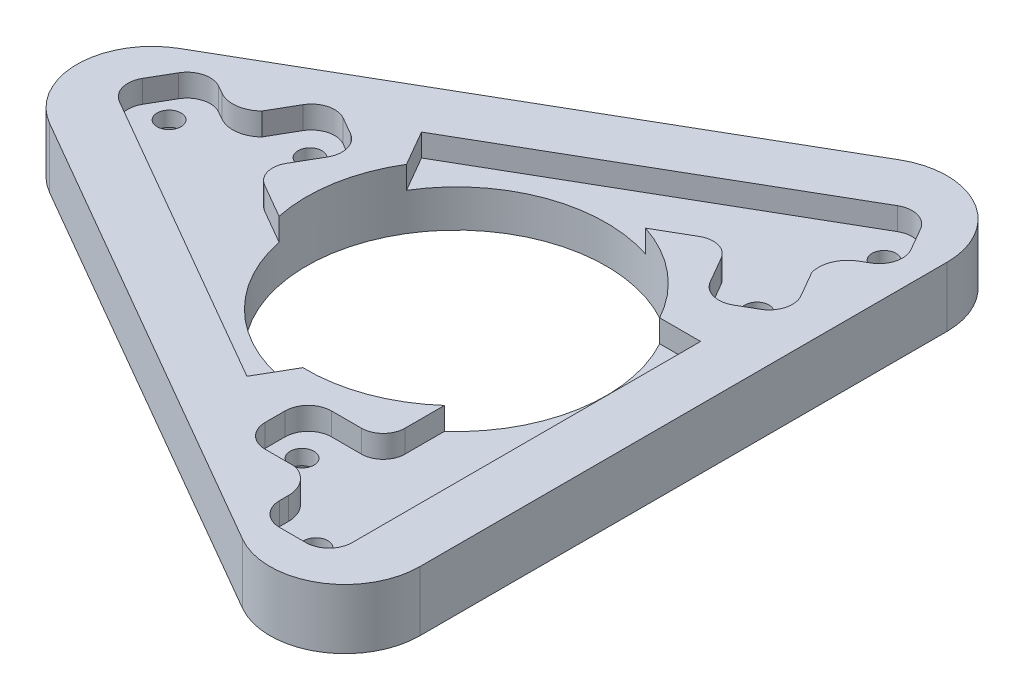
SolidWorks part; units mm, degrees
ref_plane "Plan de face" through (0, 0, 0) normal (0, 0, 1) x (1, 0, 0)
ref_plane "Plan de dessus" through (0, 0, 0) normal (0, 1, 0) x (1, 0, 0)
ref_plane "Plan de droite" through (0, 0, 0) normal (1, 0, 0) x (0, 0, -1)
sketch "Esquisse1" plane through (0, 0, 0) normal (0, 1, 0) x (1, 0, 0)
  line L7 (14.4338, 0) -> (-7.2169, 12.5) construction
  line L8 (-7.2169, 12.5) -> (-7.2169, -12.5) construction
  line L9 (-7.2169, -12.5) -> (14.4338, 0) construction
  circle A0 centre (0, 0) radius 7.2169 construction
  circle A1 centre (-7.2169, -12.5) radius 2 construction
  circle A2 centre (-7.2169, 12.5) radius 2 construction
  circle A3 centre (14.4338, 0) radius 2 construction
  dimension "D2" = 4
  dimension "D3" = 4
  dimension "D4" = 4
  dimension "D1" = 25
sketch "Esquisse4" plane through (0, 0, 0) normal (0, 1, 0) x (1, 0, 0)
  line L0 (14.8238, 7.28) -> (16.4238, 7.28) construction
  line L1 (16.4238, 7.28) -> (16.4238, -22.72) construction
  line L2 (16.4238, -22.72) -> (14.8238, -22.72) construction
  line L3 (14.8238, -22.72) -> (14.8238, 7.28) construction
  line L7 (-1.1072, -16.4777) -> (-27.088, -1.4777) construction
  line L8 (-27.088, -1.4777) -> (-27.888, -2.8634) construction
  line L9 (-7.2169, 12.5) -> (-7.2169, -12.5) construction
  line L10 (-13.7165, 9.1977) -> (-14.5165, 10.5834) construction
  line L11 (-14.5165, 10.5834) -> (11.4642, 25.5834) construction
  line L12 (11.4642, 25.5834) -> (12.2642, 24.1977) construction
  line L13 (12.2642, 24.1977) -> (-13.7165, 9.1977) construction
  line L14 (-7.2169, -12.5) -> (14.4338, 0) construction
  line L15 (-27.888, -2.8634) -> (-1.9072, -17.8634) construction
  line L16 (-1.9072, -17.8634) -> (-1.1072, -16.4777) construction
  dimension "D2" = 1.6
  dimension "D3" = 30
  dimension "D4" = 7.28
  dimension "D5" = 0.39
  dimension "D6" = 60
  dimension "D7" = 0.39
  dimension "D8" = 1.6
  dimension "D9" = 1.6
  dimension "D10" = 0.39
  dimension "D11" = 7.28
  dimension "D12" = 30
  dimension "D13" = 1.6
  dimension "D14" = 7.28
  dimension "D15" = 30
  dimension "D16" = 1.6
  dimension "D17" = 60
sketch "Esquisse5" plane through (0, 0, 0) normal (0, 1, 0) x (1, 0, 0)
  line L0 (-7.2169, 12.5) -> (-7.2169, -12.5) construction
  line L1 (30.3109, -52.5) -> (30.3109, 52.5)
  line L2 (30.3109, 52.5) -> (-60.6218, 0)
  line L3 (-60.6218, 0) -> (30.3109, -52.5)
  circle A1 centre (0, 0) radius 20
  circle A2 centre (0, 0) radius 30.3109 construction
  dimension "D1" = 105
  dimension "D2" = 40
extrude "Boss.-Extru.1" add sketch "Esquisse5" along normal blind 8
ref_axis "Axe1" through (0, 130.0156, 0) along (0, -1, 0)
sketch "Esquisse8" plane through (0, 8, 0) normal (0, 1, 0) x (1, 0, 0)
  line L32 (-32.788, 6.8938) -> (-30.788, 10.3579) construction
  line L33 (-44.5284, 2.7025) -> (-42.7784, 5.7336) construction
  line L36 (-38.6803, 6.8317) -> (-37.6693, 6.2479) construction
  line L37 (-24.1899, -1.5344) -> (1.4928, -16.3623) construction
  line L40 (1.4928, -16.3623) -> (-3.2572, -24.5895) construction
  line L41 (-13.1835, -18.8586) -> (3.6691, -28.5884) construction
  line L52 (-3.2572, -24.5895) -> (1.4928, -16.3623) construction
  line L53 (-3.2572, -24.5895) -> (-43.4303, -1.3956) construction
  line L54 (-26.6899, 11.456) -> (-24.3861, 10.1259) construction
  line L55 (-23.288, 6.0278) -> (-25.288, 2.5637) construction
  line L56 (-25.288, 2.5637) -> (-23.288, 6.0278) construction
  line L82 (-32.868, 6.9552) -> (-30.8746, 10.4079)
  line L83 (-26.6399, 11.5426) -> (-24.3361, 10.2125)
  line L84 (-23.2014, 5.9778) -> (-25.2014, 2.5137)
  line L85 (-24.1399, -1.4478) -> (1.6294, -16.3257)
  line L86 (1.6294, -16.3257) -> (-3.2206, -24.7261)
  line L87 (-3.2206, -24.7261) -> (-43.4803, -1.4822)
  line L88 (-44.615, 2.7525) -> (-42.865, 5.7836)
  line L89 (-38.6303, 6.9183) -> (-37.6193, 6.3345)
  line L112 (22.4574, 24.9869) -> (24.4508, 21.5342)
  line L113 (23.3161, 17.2995) -> (21.0123, 15.9694)
  line L114 (16.7776, 17.1041) -> (14.7776, 20.5682)
  line L115 (10.8161, 21.6297) -> (-14.9531, 6.7517)
  line L116 (-14.9531, 6.7517) -> (-19.8031, 15.1522)
  line L117 (-19.8031, 15.1522) -> (20.4565, 38.3961)
  line L118 (24.6912, 37.2614) -> (26.4412, 34.2304)
  line L119 (25.3065, 29.9957) -> (24.2955, 29.412)
  line L128 (22.3642, 24.9483) -> (24.3642, 21.4842) construction
  line L129 (24.6046, 37.2114) -> (26.3546, 34.1804) construction
  line L130 (25.2565, 30.0823) -> (24.2455, 29.4986) construction
  line L131 (10.7661, 21.7163) -> (-14.9165, 6.8883) construction
  line L132 (-14.9165, 6.8883) -> (-19.6665, 15.1156) construction
  line L133 (-19.6665, 15.1156) -> (20.5065, 38.3095) construction
  line L134 (23.2661, 17.3861) -> (20.9623, 16.056) construction
  line L135 (16.8642, 17.1541) -> (14.8642, 20.6182) construction
  line L136 (10.4106, -31.9421) -> (6.4238, -31.9421)
  line L137 (3.3238, -28.8421) -> (3.3238, -26.1819)
  line L138 (6.4238, -23.0819) -> (10.4238, -23.0819)
  line L139 (13.3238, -20.1819) -> (13.3238, 9.5739)
  line L140 (13.3238, 9.5739) -> (23.0238, 9.5739)
  line L141 (23.0238, 9.5739) -> (23.0238, -36.9139)
  line L142 (19.9238, -40.0139) -> (16.4238, -40.0139)
  line L143 (13.3238, -36.9139) -> (13.3238, -35.7465)
  line L144 (10.4238, -31.8421) -> (6.4238, -31.8421) construction
  line L145 (19.9238, -39.9139) -> (16.4238, -39.9139) construction
  line L146 (13.4238, -36.9139) -> (13.4238, -35.7465) construction
  line L147 (13.4238, -20.1819) -> (13.4238, 9.4739) construction
  line L148 (13.4238, 9.4739) -> (22.9238, 9.4739) construction
  line L149 (22.9238, 9.4739) -> (22.9238, -36.9139) construction
  line L150 (3.4238, -28.8421) -> (3.4238, -26.1819) construction
  line L151 (6.4238, -23.1819) -> (10.4238, -23.1819) construction
  arc A8 (-43.4303, -1.3956) -> (-44.5284, 2.7025) centre (-41.9303, 1.2025) cw construction
  arc A10 (-42.7784, 5.7336) -> (-38.6803, 6.8317) centre (-40.1803, 4.2336) cw construction
  arc A11 (-37.6693, 6.2479) -> (-32.788, 6.8938) centre (-35.6489, 9.7473) ccw construction
  arc A12 (-25.288, 2.5637) -> (-25.6873, 1.1888) centre (-22.6899, 1.0637) ccw construction
  arc A13 (-30.788, 10.3579) -> (-26.6899, 11.456) centre (-28.1899, 8.8579) cw construction
  arc A14 (-24.3861, 10.1259) -> (-23.288, 6.0278) centre (-25.8861, 7.5278) cw construction
  arc A15 (-25.288, 2.5637) -> (-24.1899, -1.5344) centre (-22.6899, 1.0637) ccw construction
  arc A28 (-30.8746, 10.4079) -> (-26.6399, 11.5426) centre (-28.1899, 8.8579) cw
  arc A29 (-24.3361, 10.2125) -> (-23.2014, 5.9778) centre (-25.8861, 7.5278) cw
  arc A30 (-25.2014, 2.5137) -> (-24.1399, -1.4478) centre (-22.6899, 1.0637) ccw
  arc A31 (-43.4803, -1.4822) -> (-44.615, 2.7525) centre (-41.9303, 1.2025) cw
  arc A32 (-42.865, 5.7836) -> (-38.6303, 6.9183) centre (-40.1803, 4.2336) cw
  arc A33 (-37.6193, 6.3345) -> (-32.868, 6.9552) centre (-35.6489, 9.7473) ccw
  arc A52 (24.4508, 21.5342) -> (23.3161, 17.2995) centre (21.7661, 19.9842) cw
  arc A53 (21.0123, 15.9694) -> (16.7776, 17.1041) centre (19.4623, 18.6541) cw
  arc A54 (14.7776, 20.5682) -> (10.8161, 21.6297) centre (12.2661, 19.1182) ccw
  arc A55 (20.4565, 38.3961) -> (24.6912, 37.2614) centre (22.0065, 35.7114) cw
  arc A56 (26.4412, 34.2304) -> (25.3065, 29.9957) centre (23.7565, 32.6804) cw
  arc A57 (24.2955, 29.412) -> (22.4574, 24.9869) centre (26.2658, 25.9992) ccw
  arc A64 (20.5065, 38.3095) -> (24.6046, 37.2114) centre (22.0065, 35.7114) cw construction
  arc A65 (26.3546, 34.1804) -> (25.2565, 30.0823) centre (23.7565, 32.6804) cw construction
  arc A66 (24.2455, 29.4986) -> (22.3642, 24.9483) centre (26.2658, 25.9992) ccw construction
  arc A67 (24.3642, 21.4842) -> (23.2661, 17.3861) centre (21.7661, 19.9842) cw construction
  arc A68 (20.9623, 16.056) -> (16.8642, 17.1541) centre (19.4623, 18.6541) cw construction
  arc A69 (14.8642, 20.6182) -> (10.7661, 21.7163) centre (12.2661, 19.1182) ccw construction
  arc A70 (6.4238, -31.9421) -> (3.3238, -28.8421) centre (6.4238, -28.8421) cw
  arc A71 (3.3238, -26.1819) -> (6.4238, -23.0819) centre (6.4238, -26.1819) cw
  arc A72 (10.4238, -23.0819) -> (13.3238, -20.1819) centre (10.4238, -20.1819) ccw
  arc A73 (23.0238, -36.9139) -> (19.9238, -40.0139) centre (19.9238, -36.9139) cw
  arc A74 (16.4238, -40.0139) -> (13.3238, -36.9139) centre (16.4238, -36.9139) cw
  arc A75 (13.3238, -35.7465) -> (10.4106, -31.9421) centre (9.3831, -35.7465) ccw
  arc A76 (22.9238, -36.9139) -> (19.9238, -39.9139) centre (19.9238, -36.9139) cw construction
  arc A77 (16.4238, -39.9139) -> (13.4238, -36.9139) centre (16.4238, -36.9139) cw construction
  arc A78 (13.4238, -35.7465) -> (10.4238, -31.8421) centre (9.3831, -35.7465) ccw construction
  arc A79 (6.4238, -31.8421) -> (3.4238, -28.8421) centre (6.4238, -28.8421) cw construction
  arc A80 (3.4238, -26.1819) -> (6.4238, -23.1819) centre (6.4238, -26.1819) cw construction
  arc A81 (10.4238, -23.1819) -> (13.4238, -20.1819) centre (10.4238, -20.1819) ccw construction
  point P31 (-0.75, -1.299)
  point P35 (0.75, -1.299)
  point P108 (1.4434, -0.8333)
  point P148 (0, 1.6667)
  point P150 (-1.4434, -0.8333)
  point P151 (0, 0)
  dimension "D1" = 0.1
extrude "Enlèv. mat.-Extru.1" cut sketch "Esquisse8" against normal blind 3
hole_wizard "Dégagement M32" positions "Esquisse13" profile "Esquisse14" hole size "M3" standard "Ansi Metric" end condition through all
sketch "Esquisse13" plane through (0, 5, 0) normal (0, 1, 0) x (1, 0, 0)
  line L0 (22.9238, -36.9139) -> (13.4238, -36.9139) construction
  point P9 (-41.0553, 2.718)
  point P12 (-27.288, 7.7599)
  point P15 (20.3642, 19.7522)
  point P18 (22.8815, 34.1959)
  point P21 (6.9238, -27.512)
  point P27 (18.1738, -36.9139)
sketch "Esquisse14" plane through (-41.0553, 5, -2.718) normal (1, 0, 0) x (0, 0, 1)
  line L0 (0, 0) -> (0, 5)
  line L1 (0, 5) -> (1.6, 5)
  line L2 (1.6, 5) -> (1.6, 0)
  line L5 (1.6, 0) -> (0, 0)
  line L11 (0, -6.35) -> (0, 107.95) construction
  dimension "Diamètre du perçage jusqu'au prochain" = 3.2
  dimension "Profondeur du perçage jusqu'au prochain" = 5
sketch "Esquisse15" plane through (0, 0, 0) normal (0, -1, 0) x (-1, 0, 0)
  line L0 (-3.4238, -27.512) -> (-10.4238, -27.512) construction
  line L1 (40.2905, -0.4234) -> (43.3934, 0.485)
  line L2 (43.3934, 0.485) -> (44.1582, 3.6264)
  line L3 (44.1582, 3.6264) -> (41.8201, 5.8594)
  line L4 (41.8201, 5.8594) -> (38.7171, 4.9511)
  line L5 (38.7171, 4.9511) -> (37.9523, 1.8097)
  line L6 (37.9523, 1.8097) -> (40.2905, -0.4234)
  line L7 (-25.9002, 35.3539) -> (-25.3937, 32.1607)
  line L8 (-25.3937, 32.1607) -> (-22.3751, 31.0026)
  line L9 (-22.3751, 31.0026) -> (-19.8629, 33.0379)
  line L10 (-19.8629, 33.0379) -> (-20.3693, 36.2311)
  line L11 (-20.3693, 36.2311) -> (-23.388, 37.3892)
  line L12 (-23.388, 37.3892) -> (-25.9002, 35.3539)
  line L13 (-21.2639, -37.865) -> (-18.8951, -40.0656)
  line L14 (-18.8951, -40.0656) -> (-15.805, -39.1145)
  line L15 (-15.805, -39.1145) -> (-15.0837, -35.9628)
  line L16 (-15.0837, -35.9628) -> (-17.4524, -33.7623)
  line L17 (-17.4524, -33.7623) -> (-20.5425, -34.7134)
  line L18 (-20.5425, -34.7134) -> (-21.2639, -37.865)
  line L19 (-3.6906, -27.512) -> (-5.3072, -24.712)
  line L20 (-5.3072, -24.712) -> (-8.5403, -24.712)
  line L21 (-8.5403, -24.712) -> (-10.1569, -27.512)
  line L22 (-10.1569, -27.512) -> (-8.5403, -30.312)
  line L23 (-8.5403, -30.312) -> (-5.3072, -30.312)
  line L24 (-5.3072, -30.312) -> (-3.6906, -27.512)
  line L26 (29.9325, 5.8997) -> (30.2211, 9.12)
  line L27 (30.2211, 9.12) -> (27.5766, 10.9801)
  line L28 (27.5766, 10.9801) -> (24.6435, 9.62)
  line L29 (24.6435, 9.62) -> (24.3548, 6.3997)
  line L30 (24.3548, 6.3997) -> (26.9993, 4.5396)
  line L31 (26.9993, 4.5396) -> (29.9325, 5.8997)
  line L32 (-17.7197, 21.6123) -> (-20.6529, 22.9724)
  line L33 (-20.6529, 22.9724) -> (-23.2974, 21.1123)
  line L34 (-23.2974, 21.1123) -> (-23.0087, 17.892)
  line L35 (-23.0087, 17.892) -> (-20.0755, 16.5319)
  line L36 (-20.0755, 16.5319) -> (-17.4311, 18.392)
  line L37 (-17.4311, 18.392) -> (-17.7197, 21.6123)
  circle A0 centre (41.0553, 2.718) radius 2.8 construction
  circle A1 centre (-22.8815, 34.1959) radius 2.8 construction
  circle A2 centre (-18.1738, -36.9139) radius 2.8 construction
  circle A3 centre (-6.9238, -27.512) radius 2.8 construction
  circle A4 centre (27.288, 7.7599) radius 2.8 construction
  circle A5 centre (-20.3642, 19.7522) radius 2.8 construction
  point P50 (-6.9238, -24.712)
  point P59 (25.6771, 5.4697)
  dimension "D1" = 5.6
  dimension "D2" = 5.6
  dimension "D3" = 5.6
  dimension "D4" = 5.6
  dimension "D5" = 5.6
  dimension "D6" = 5.6
extrude "Enlèv. mat.-Extru.3" cut sketch "Esquisse15" against normal blind 3
fillet "Congé1" radius 10 3 edges at (30.3109, 4, -52.5) (30.3109, 4, 52.5) (-60.6218, 4, 0)
sketch "Esquisse18" plane through (0, 0, 0) normal (0, 1, 0) x (-1, 0, 0)
  line L7 (-88.6339, -70.13) -> (-88.6339, 68.2127) construction
  line L22 (-34.3358, -17.4522) -> (-34.3358, -37.04)
  line L23 (-39.2388, -17.4522) -> (-34.3358, -17.4522)
  line L24 (-39.2388, -19.4522) -> (-39.2388, -17.4522)
  line L25 (-56.3358, -29.2997) -> (-48.3358, -29.2997)
  line L26 (-59.3358, -33.2997) -> (-59.3358, -32.2997)
  line L27 (-42.1643, -36.2997) -> (-56.3358, -36.2997)
  line L28 (-36.9216, -40.7139) -> (-40.7501, -36.8855)
  line L29 (-36.3358, -45.2997) -> (-36.3358, -42.1282)
  line L30 (-32.3358, -55.2997) -> (-32.3358, -50.1987)
  line L31 (-32.3358, -55.2997) -> (-19.3358, -45.7003)
  line L32 (-35.6712, 15.6092) -> (-30.7683, 15.6092)
  line L33 (-35.6712, 17.6092) -> (-35.6712, 15.6092)
  line L34 (-30.7683, 15.6092) -> (-30.7683, 35.2997)
  line L35 (-55.7683, 31.4568) -> (-55.7683, 30.4568)
  line L36 (-52.7683, 27.4568) -> (-44.7683, 27.4568)
  line L37 (-38.5967, 34.4568) -> (-52.7683, 34.4568)
  line L38 (-33.3541, 38.871) -> (-37.1825, 35.0425)
  line L39 (-32.7683, 43.4568) -> (-32.7683, 40.2852)
  line L40 (-28.7683, 49.4568) -> (-28.7683, 48.3557)
  line L41 (-28.7683, 49.4568) -> (-25.7683, 43.96)
  arc A19 (-37.1825, 35.0425) -> (-38.5967, 34.4568) centre (-38.5967, 36.4568) cw
  arc A20 (-32.7683, 40.2852) -> (-33.3541, 38.871) centre (-34.7683, 40.2852) cw
  arc A21 (-34.3358, -37.04) -> (-19.3358, -45.7003) centre (-24.3358, -37.04) ccw
  arc A22 (-37.4193, -22.2827) -> (-39.2388, -19.4522) centre (-39.2388, -21.4522) ccw
  arc A23 (-48.3358, -29.2997) -> (-37.4193, -22.2827) centre (-48.3358, -17.2997) ccw
  arc A24 (-59.3358, -32.2997) -> (-56.3358, -29.2997) centre (-56.3358, -32.2997) cw
  arc A25 (-56.3358, -36.2997) -> (-59.3358, -33.2997) centre (-56.3358, -33.2997) cw
  arc A26 (-40.7501, -36.8855) -> (-42.1643, -36.2997) centre (-42.1643, -38.2997) ccw
  arc A27 (-36.3358, -42.1282) -> (-36.9216, -40.7139) centre (-38.3358, -42.1282) ccw
  arc A28 (-33.9358, -48.2391) -> (-36.3358, -45.2997) centre (-33.3358, -45.2997) cw
  arc A29 (-32.3358, -50.1987) -> (-33.9358, -48.2391) centre (-34.3358, -50.1987) ccw
  arc A30 (-33.8518, 20.4397) -> (-35.6712, 17.6092) centre (-35.6712, 19.6092) cw
  arc A31 (-30.7683, 35.2997) -> (-25.7683, 43.96) centre (-20.7683, 35.2997) cw
  arc A32 (-44.7683, 27.4568) -> (-33.8518, 20.4397) centre (-44.7683, 15.4568) cw
  arc A33 (-52.7683, 27.4568) -> (-55.7683, 30.4568) centre (-52.7683, 30.4568) cw
  arc A34 (-52.7683, 34.4568) -> (-55.7683, 31.4568) centre (-52.7683, 31.4568) ccw
  arc A35 (-30.3683, 46.3961) -> (-32.7683, 43.4568) centre (-29.7683, 43.4568) ccw
  arc A36 (-28.7683, 48.3557) -> (-30.3683, 46.3961) centre (-30.7683, 48.3557) cw
  point P0 (0, 0)
  dimension "D4" = 2
  dimension "D5" = 12
  dimension "D7" = 3
  dimension "D9" = 3
  dimension "D11" = 2
  dimension "D13" = 2
  dimension "D15" = 3
  dimension "D16" = 2
  dimension "D19" = 10
  dimension "D24" = 4.9029
  dimension "D25" = 14
  dimension "D27" = 22
  dimension "D28" = 22
  dimension "D29" = 7.8284
  dimension "D1" = 4.9029
  dimension "D2" = 2
  dimension "D3" = 19.5878
  dimension "D6" = 8
  dimension "D8" = 1
  dimension "D10" = 14.1716
  dimension "D12" = 5.4142
  dimension "D14" = 3.1716
  dimension "D17" = 5.101
  dimension "D18" = 16.1601
  dimension "D20" = 19.5878
  dimension "D21" = 90
  dimension "D22" = 90
  dimension "D23" = 53.557
  dimension "D26" = 14
  dimension "D30" = 45
  dimension "D31" = 1
  dimension "D32" = 20.6759
  dimension "D33" = 5.4142
  dimension "D34" = 9
  dimension "D35" = 1
  dimension "D36" = 13.1587
